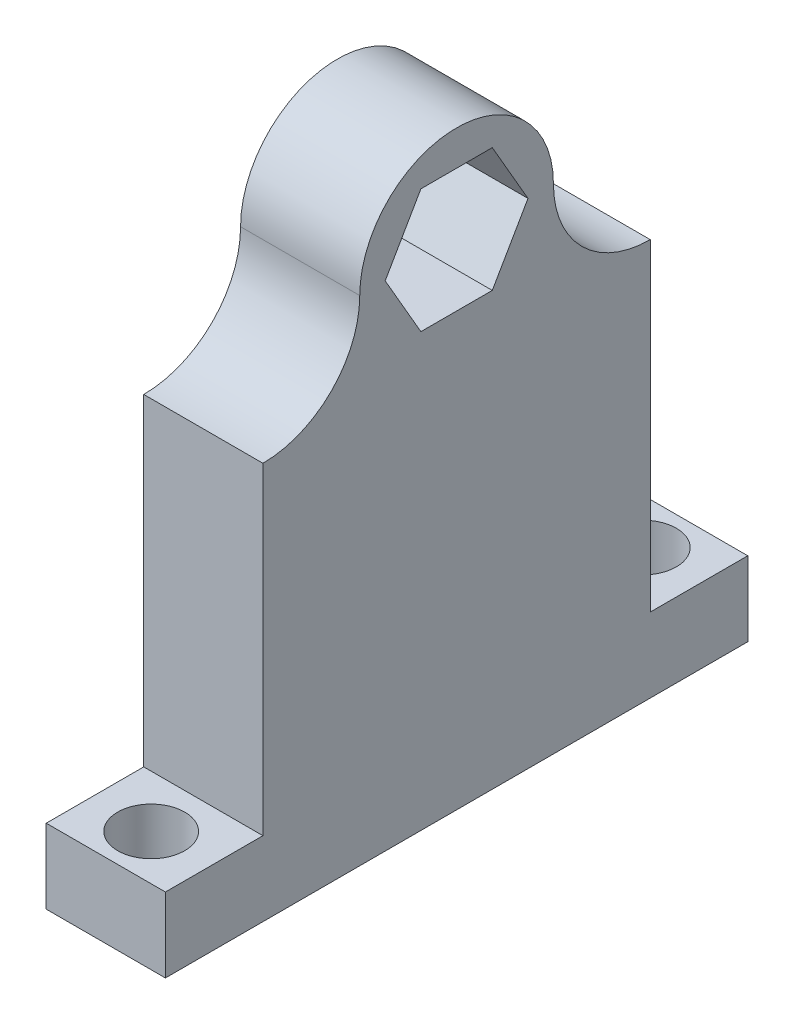
SolidWorks part; units mm, degrees
ref_plane "Спереди" through (0, 0, 0) normal (0, 0, 1) x (1, 0, 0)
ref_plane "Сверху" through (0, 0, 0) normal (0, 1, 0) x (1, 0, 0)
ref_plane "Справа" through (0, 0, 0) normal (1, 0, 0) x (0, 0, -1)
sketch "Эскиз1" plane through (0, 0, 0) normal (1, 0, 0) x (0, 0, -1)
  line L6 (-6.5, 0) -> (6.5, 0) construction
  line L12 (-13, -6.5) -> (-13, -11.5)
  line L13 (13, -6.5) -> (13, -11.5)
  line L15 (-13, -11.5) -> (13, -11.5)
  arc A0 (6.5, 0) -> (-6.5, 0) centre (0, 0) ccw
  arc A1 (-13, -6.5) -> (-6.5, 0) centre (-13, 0) ccw
  arc A2 (6.5, 0) -> (13, -6.5) centre (13, 0) ccw
  point P4 (0, 0)
  point P7 (0, -39.795)
  point P9 (0, 6.5)
  dimension "D1" = 13
  dimension "D4" = 13
  dimension "D5" = 13
  dimension "D2" = 5
extrude "Бобышка-Вытянуть1" add sketch "Эскиз1" along normal blind 8
sketch "Эскиз2" plane through (8, 0, 0) normal (1, 0, 0) x (0, 0, -1)
  line L1 (4.792, 0) -> (2.396, 4.15)
  line L2 (2.396, 4.15) -> (-2.396, 4.15)
  line L3 (-2.396, 4.15) -> (-4.792, 0)
  line L4 (-4.792, 0) -> (-2.396, -4.15)
  line L5 (-2.396, -4.15) -> (2.396, -4.15)
  line L6 (2.396, -4.15) -> (4.792, 0)
  circle A0 centre (0, 0) radius 4.15 construction
  dimension "D1" = 8.3
extrude "Вырез-Вытянуть1" cut sketch "Эскиз2" against normal through all
sketch "Эскиз4" plane through (0, -11.5, 0) normal (0, -1, 0) x (1, 0, 0)
  line L8 (0, 13) -> (0, -13)
  line L9 (0, -13) -> (8, -13)
  line L10 (8, -13) -> (8, 13)
  line L11 (8, 13) -> (0, 13)
  line L12 (0, 13) -> (0, -13)
  line L13 (0, -13) -> (8, -13)
  line L14 (8, -13) -> (8, 13)
  line L15 (8, 13) -> (0, 13)
  dimension "D1" = 0
extrude "Бобышка-Вытянуть2" add sketch "Эскиз4" along normal up to surface (21.65 mm away)
sketch "Эскиз5" plane through (0, -33.15, 0) normal (0, -1, 0) x (1, 0, 0)
  line L1 (0, 19.5455) -> (8, 19.5455)
  line L2 (0, 19.5455) -> (0, -19.5455)
  line L3 (0, -19.5455) -> (8, -19.5455)
  line L4 (8, 19.5455) -> (8, -19.5455)
  line L8 (4, -16.5) -> (4, 16.5) construction
  line L9 (8, -19.5455) -> (0, 19.5455) construction
  line L10 (0, -19.5455) -> (8, 19.5455) construction
  circle A0 centre (4, -16.5) radius 2.25
  circle A1 centre (4, 16.5) radius 2.25
  dimension "Диаметр001" = 4.5
  dimension "Диаметр002" = 4.5
  dimension "X001" = 4
  dimension "X002" = 4
  dimension "Y001" = 19.5455
  dimension "Y002" = 3.0455
  dimension "Y003" = 33
  dimension "Y004" = 3.0455
extrude "Бобышка-Вытянуть3" add sketch "Эскиз5" against normal blind 5
ref_axis "Ось_крепления_гайки_33" through (4, -33.15, -16.5) along (0, 1, 0)
ref_axis "Ось_крепления_гайки_34" through (4, -33.15, 16.5) along (0, 1, 0)
